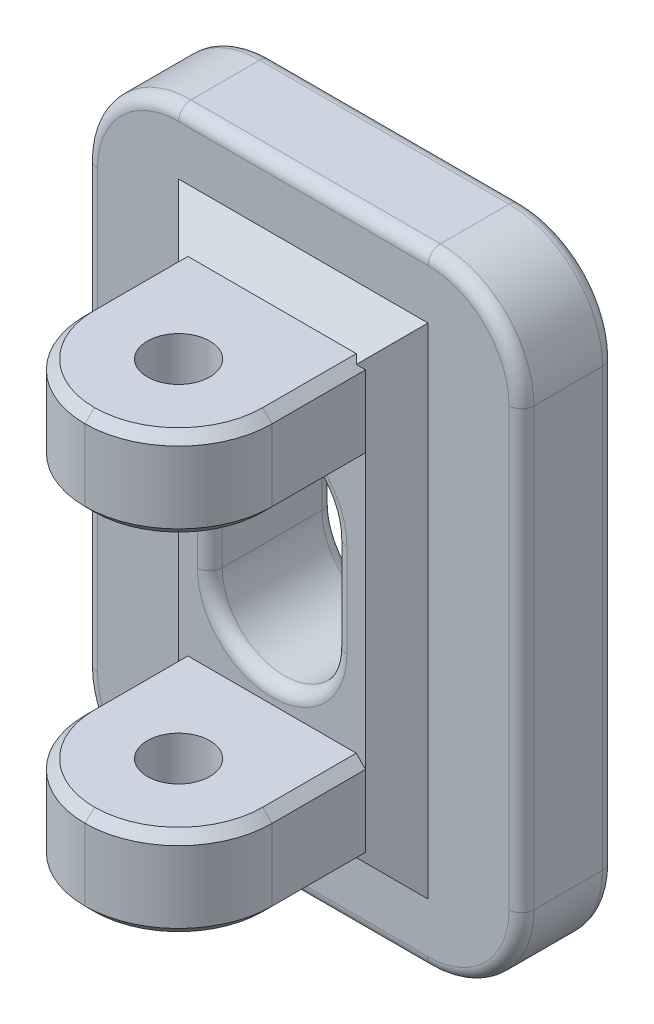
SolidWorks part; units mm, degrees
ref_plane "Front Plane" through (0, 0, 0) normal (0, 0, 1) x (1, 0, 0)
ref_plane "Top Plane" through (0, 0, 0) normal (0, 1, 0) x (1, 0, 0)
ref_plane "Right Plane" through (0, 0, 0) normal (1, 0, 0) x (0, 0, -1)
sketch "Sketch1" plane through (0, 0, 0) normal (0, 0, 1) x (1, 0, 0)
  line L1 (-4, -10) -> (4, -10)
  line L2 (-7, -7) -> (-7, 7)
  line L3 (-4, 10) -> (4, 10)
  line L4 (7, -7) -> (7, 7)
  line L5 (-7, -10) -> (7, 10) construction
  line L6 (-7, 10) -> (7, -10) construction
  arc A0 (-4, -10) -> (-7, -7) centre (-4, -7) cw
  arc A1 (4, -10) -> (7, -7) centre (4, -7) ccw
  arc A2 (4, 10) -> (7, 7) centre (4, 7) cw
  arc A3 (-7, 7) -> (-4, 10) centre (-4, 7) cw
  point P0 (0, 0)
  dimension "D3" = 3
  dimension "D1" = 20
  dimension "D2" = 14
extrude "Boss-Extrude1" add sketch "Sketch1" along normal blind 3 contours A3 L2 A0 L1 A1 L4 A2 L3
sketch "Sketch2" plane through (0, 0, 3) normal (0, 0, 1) x (1, 0, 0)
  line L1 (-3, -7) -> (3, -7)
  line L2 (-3, -7) -> (-3, 7)
  line L3 (-3, 7) -> (3, 7)
  line L4 (3, -7) -> (3, 7)
  line L5 (-3, -7) -> (3, 7) construction
  line L6 (-3, 7) -> (3, -7) construction
  point P0 (0, 0)
  dimension "D1" = 14
  dimension "D2" = 6
extrude "Boss-Extrude2" add sketch "Sketch2" along normal blind 1
sketch "Sketch3" plane through (0, 0, 4) normal (0, 0, 1) x (1, 0, 0)
  line L0 (3, -7) -> (3, 7) construction
  line L1 (-3, 7) -> (3, 7)
  line L2 (-3, 7) -> (-3, 4.1)
  line L3 (-3, 4.1) -> (3, 4.1)
  line L4 (3, 7) -> (3, 4.1)
  line L6 (-3, -7) -> (3, -7)
  line L7 (-3, -7) -> (-3, -4.1)
  line L8 (-3, -4.1) -> (3, -4.1)
  line L9 (3, -7) -> (3, -4.1)
  dimension "D1" = 8.2
  dimension "D2" = 4.1
extrude "Boss-Extrude3" add sketch "Sketch3" along normal blind 6
sketch "Sketch4" plane through (0, 7, 0) normal (0, 1, 0) x (1, 0, 0)
  circle A0 centre (0, -7) radius 3 construction
  circle A1 centre (0, -7) radius 1
  dimension "D1" = 2
extrude "Cut-Extrude1" cut sketch "Sketch4" against normal through all
fillet "Fillet1" radius 3 4 edges at (3, -5.55, 10) (-3, -5.55, 10) (-3, 5.55, 10) (3, 5.55, 10)
chamfer "Chamfer1" distance 1 angle 45 4 edges at (0, -7, 3) (3, 0, 3) (-3, 0, 3) (0, 7, 3)
chamfer "Chamfer2" distance 0.3 angle 45 16 edges at (3, -7, 5.5) (2.1213, -7, 9.1213) (-2.1213, -7, 9.1213) (-3, -7, 5.5) (3, -4.1, 5.5) (2.1213, -4.1, 9.1213) (-2.1213, -4.1, 9.1213) (-3, -4.1, 5.5) (3, 4.1, 5.5) (2.1213, 4.1, 9.1213) (-3, 4.1, 5.5) (-2.1213, 4.1, 9.1213) (3, 7, 5.5) (2.1213, 7, 9.1213) (-2.1213, 7, 9.1213) (-3, 7, 5.5)
sketch "Sketch5" plane through (0, 0, 4) normal (0, 0, 1) x (1, 0, 0)
  line L0 (0, -1.5) -> (0, 1.5) construction
  line L2 (-2, -1.5) -> (-2, 1.5)
  line L3 (2, -1.5) -> (2, 1.5)
  arc A0 (-2, -1.5) -> (2, -1.5) centre (0, -1.5) ccw
  arc A1 (2, 1.5) -> (-2, 1.5) centre (0, 1.5) ccw
  point P5 (0, 0)
  dimension "D2" = 2
  dimension "D1" = 3
extrude "Cut-Extrude2" cut sketch "Sketch5" against normal through all
fillet "Fillet2" radius 0.4 24 edges at (-7, 0, 0) (-6.1213, -9.1213, 0) (0, -10, 0) (6.1213, -9.1213, 0) (7, 0, 0) (6.1213, 9.1213, 0) (0, 10, 0) (-7, 0, 3) (-6.1213, -9.1213, 3) (0, -10, 3) (6.1213, -9.1213, 3) (7, 0, 3) (6.1213, 9.1213, 3) (0, 10, 3) (-6.1213, 9.1213, 0) (-6.1213, 9.1213, 3) (0, 3.5, 0) (2, 0, 0) (0, -3.5, 0) (0, 3.5, 4) (2, 0, 4) (0, -3.5, 4) (-2, 0, 0) (-2, 0, 4)
